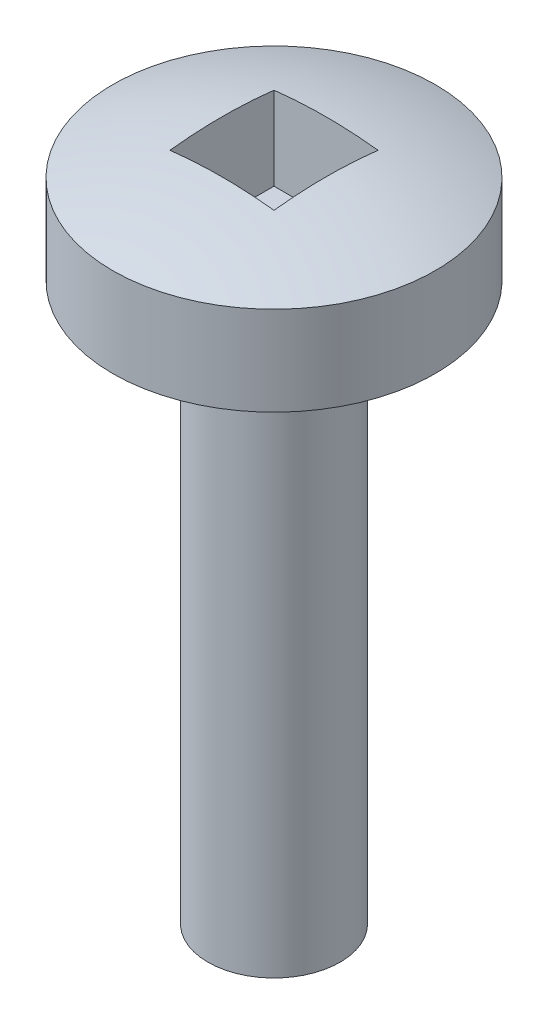
SolidWorks part; units mm, degrees
material "Cast Alloy Steel"
ref_plane "Front Plane" through (0, 0, 0) normal (0, 0, 1) x (1, 0, 0)
ref_plane "Top Plane" through (0, 0, 0) normal (0, 1, 0) x (1, 0, 0)
ref_plane "Right Plane" through (0, 0, 0) normal (1, 0, 0) x (0, 0, -1)
sketch "Sketch1" plane through (0, 0, 0) normal (0, 1, 0) x (1, 0, 0)
  circle A0 centre (0, 0) radius 1.1303
  dimension "D1" = 2.2606
extrude "threads" add sketch "Sketch1" against normal blind 9.525
sketch "Sketch2" plane through (0, 0, 0) normal (0, 1, 0) x (1, 0, 0)
  circle A0 centre (0, 0) radius 2.7559
  dimension "D1" = 5.5118
extrude "Head" add sketch "Sketch2" along normal blind 1.524
dome "HeadDome" faces to dome 1 distance 0.508 reverse direction no elliptical dome no face at (0, 1.524, 2.7559) parameters "D1"=0.508
ref_plane "DriverPlane" through (0, 2.032, 0) normal (0, 1, 0) x (1, 0, 0)
sketch "Sketch3" plane through (0, 2.032, 0) normal (0, 1, 0) x (1, 0, 0)
  line L1 (-0.889, -0.889) -> (0.889, -0.889)
  line L2 (-0.889, -0.889) -> (-0.889, 0.889)
  line L3 (-0.889, 0.889) -> (0.889, 0.889)
  line L4 (0.889, -0.889) -> (0.889, 0.889)
  line L5 (-0.889, -0.889) -> (0.889, 0.889) construction
  line L6 (-0.889, 0.889) -> (0.889, -0.889) construction
  point P0 (0, 0)
  dimension "D1" = 1.778
extrude "Driver" cut sketch "Sketch3" against normal blind 1.524
